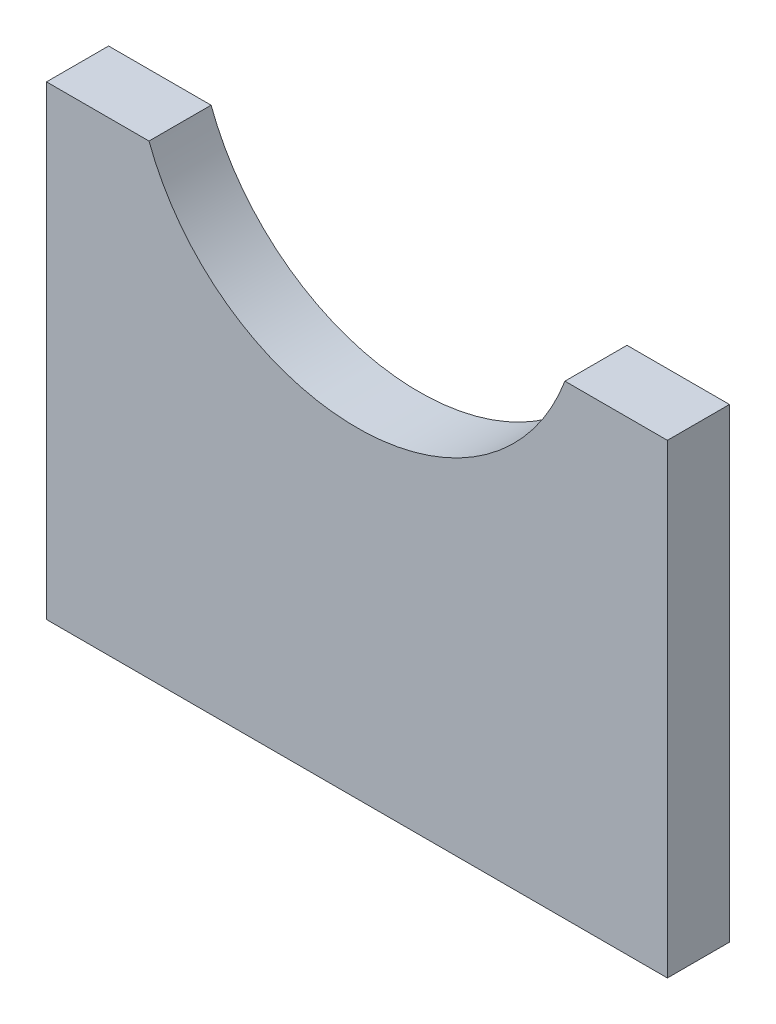
SolidWorks part; units mm, degrees
ref_plane "Front Plane" through (0, 0, 0) normal (0, 0, 1) x (1, 0, 0)
ref_plane "Top Plane" through (0, 0, 0) normal (0, 1, 0) x (1, 0, 0)
ref_plane "Right Plane" through (0, 0, 0) normal (1, 0, 0) x (0, 0, -1)
sketch "Sketch1" plane through (0, 0, -47.75) normal (0, 0, 1) x (1, 0, 0)
  line L0 (-2, 30) -> (-2, 87.9216) construction
  line L6 (-2, 30) -> (-2, 36.0304) construction
  line L15 (79, 0) -> (-79, 0) construction
  line L16 (-22, 0) -> (-22, 30)
  line L17 (-22, 0) -> (18, 0)
  line L19 (-22, 30) -> (18, 30)
  line L20 (18, 0) -> (18, 30)
  point P5 (-2, 36.0304)
  point P11 (-2, 0)
  dimension "D1" = 20
  dimension "D2" = 30
extrude "Boss-Extrude1" add sketch "Sketch1" along normal blind 4
ref_point "Point1"
ref_point "Point2"
ref_axis "Axis1" through (-2, 0, -43.75) along (0, 1, 0)
sketch "Sketch5" plane through (0, 0, -43.75) normal (0, 0, 1) x (1, 0, 0)
  circle A0 centre (-2, 35) radius 14.3
  arc A1 (11.9551, 38.1216) -> (12.0074, 32.1218) centre (-2, 35) ccw construction
  point P0 (-2, 35)
extrude "Cut-Extrude3" cut sketch "Sketch5" against normal up to next
